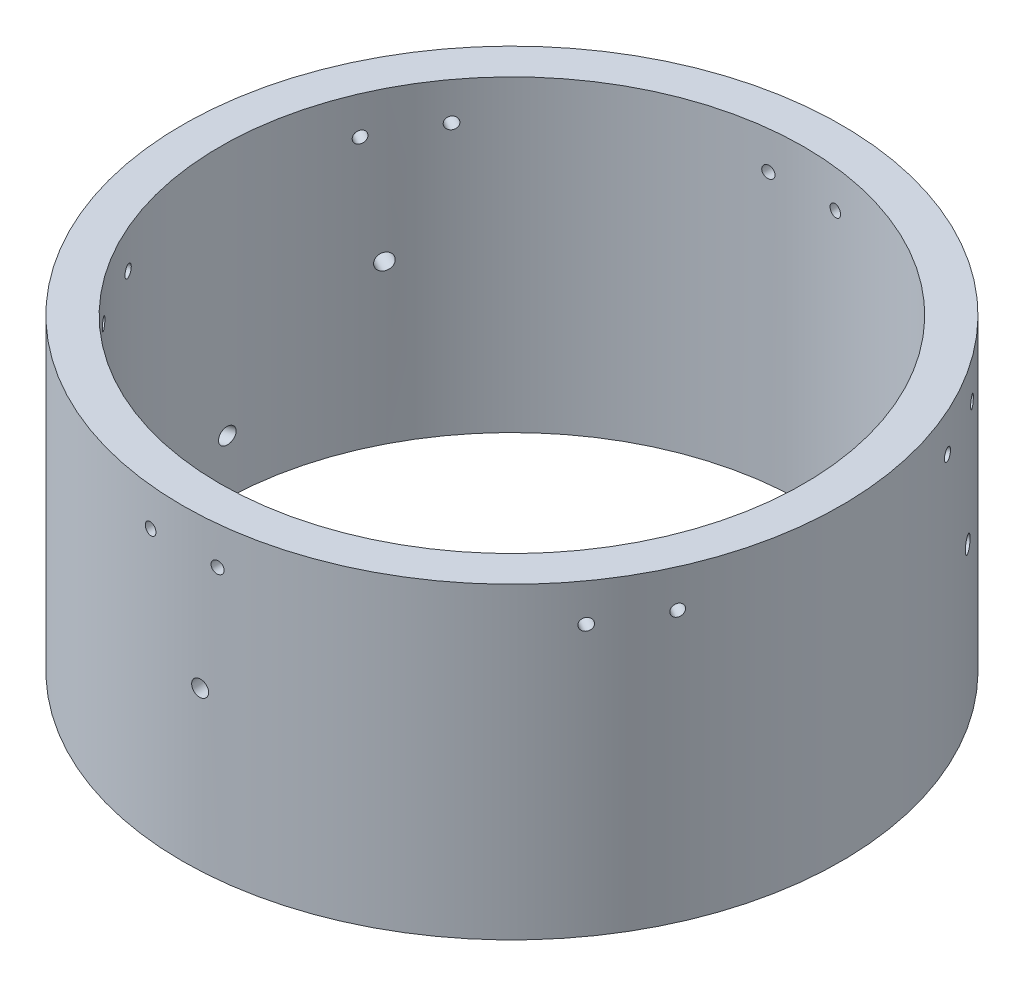
SolidWorks part; units mm, degrees
note: The reader was unsure of these and kept them because the rebuilt part matched: shared geometry of "Sketch1<6>".
material "6061 Alloy"
ref_plane "Front Plane" through (0, 0, 0) normal (0, 0, 1) x (1, 0, 0)
ref_plane "Top Plane" through (0, 0, 0) normal (0, 1, 0) x (1, 0, 0)
ref_plane "Right Plane" through (0, 0, 0) normal (1, 0, 0) x (0, 0, -1)
sketch "Sketch1" plane through (0, 0, 0) normal (0, 1, 0) x (1, 0, 0)
  line L0 (0, 0) -> (36.3914, -37.6844) construction
  line L1 (0, 0) -> (0, -26.075) construction
  line L2 (0, 0) -> (-29.7799, -10.254) construction
  circle A0 centre (0, 0) radius 49.2125
  circle A1 centre (0, 0) radius 55.5625
  circle A2 centre (36.3914, -37.6844) radius 1.0033
  dimension "D1" = 98.425
  dimension "D4" = 2.0066
  dimension "D3" = 52.3875
  dimension "D5" = 44
  dimension "D6" = 71
  dimension "D2" = 6.35
extrude "Boss-Extrude1" add sketch "Sketch1" along normal blind 51.9303 contours A2 | A1 A2 A0
sketch "Sketch2" plane through (0, 0, 0) normal (0, 0, 1) x (1, 0, 0)
  line L1 (55.5625, 51.9303) -> (-55.5625, 51.9303) construction
  line L2 (0, 0) -> (0, 58.801) construction
  line L5 (55.5625, 51.9303) -> (-55.5625, 51.9303)
  circle A0 centre (-5.6444, 45.5803) radius 1.0033
  dimension "D2" = 2.0066
  dimension "D3" = 5.6444
  dimension "D1" = 6.35
extrude "Cut-Extrude1" cut sketch "Sketch2" along normal up to surface (55.3683 mm away) contours A0
sketch "Sketch4" plane through (0, 0, 0) normal (0, 1, 0) x (1, 0, 0)
  line L0 (0, 0) -> (0, -25.6237) construction
  line L1 (0, 0) -> (1.2116, -23.1184)
  dimension "D1" = 3
ref_plane "Plane4" through (0, 0, 0) normal (0.0523, 0, 0.9986) x (0.9986, 0, -0.0523)
sketch "Sketch5" plane through (0, 0, 0) normal (0.0523, 0, 0.9986) x (0.9986, 0, -0.0523)
  circle A0 centre (0, 26.67) radius 1.3589
  dimension "D2" = 2.7178
  dimension "D1" = 26.67
extrude "Cut-Extrude5" cut sketch "Sketch5" along normal up to surface (55.5459 mm away) contours A0
mirror "Mirror1" about plane through (0, 0, 0) normal (1, 0, 0) of "Cut-Extrude1"
pattern_circular "CirPattern1" count 6 over 360 about axis through (0, 51.9303, 0) along (0, 1, 0) of "Cut-Extrude1", "Mirror1"
extrude "Cut-Extrude3" cut sketch "Sketch1<6>" along normal blind 5.08 contours A2
sketch "Sketch1<6>" plane through (0, 0, 0) normal (0, 1, 0) x (1, 0, 0) same geometry as "Sketch1"
ref_plane "Plane1" [suppressed] through (0, 25.9652, 0) normal (0, -1, 0) x (-1, 0, 0)
pattern_circular "CirPattern2" count 12 over 360 about axis through (0, 0, 0) along (0, 1, 0) of "Cut-Extrude3"
ref_plane "Plane2" through (-38.597, 0, -39.9683) normal (-0.6947, 0, -0.7193) x (-0.7193, 0, 0.6947)
pattern_circular "CirPattern3" count 3 over 360 about axis through (0, 51.9303, 0) along (0, 1, 0) of "Cut-Extrude5"
ref_plane "Plane3" through (0, 0, 0) normal (-0.9455, 0, 0.3256) x (0.3256, 0, 0.9455)
sketch "Sketch3" plane through (0, 0, 0) normal (-0.9455, 0, 0.3256) x (0.3256, 0, 0.9455)
  line L0 (0, 9.144) -> (-25.036, 9.144) construction
  line L1 (0, 9.144) -> (0, 0) construction
  circle A0 centre (0, 9.144) radius 3.6576
  circle A1 centre (-17.145, 9.144) radius 1.3589
  circle A2 centre (17.145, 9.144) radius 1.3589
  dimension "D2" = 7.3152
  dimension "D3" = 2.7178
  dimension "D1" = 9.144
  dimension "D4" = 17.145
extrude "Cut-Extrude4" cut sketch "Sketch3" along normal up to surface (55.442 mm away) contours A0 | A1 | A2
sketch "Sketch7" plane through (0, 0, 0) normal (0, -1, 0) x (1, 0, 0)
  circle A0 centre (-50.8314, 12.6737) radius 1.0033 construction
  circle A1 centre (0, 0) radius 55.5625
  circle A5 centre (0, 0) radius 55.5625
  circle A6 centre (-37.6844, 36.3914) radius 1.0033 construction
  circle A7 centre (-50.8314, 12.6737) radius 1.0033
  circle A8 centre (-37.6844, 36.3914) radius 1.0033
  arc A9 (-14.44, 50.3581) -> (12.6737, 50.8314) centre (0, 0) cw construction
  circle A10 centre (-0.9143, 52.3795) radius 1.5
  dimension "D1" = 0
  dimension "D2" = 3
extrude "Cut-Extrude6" cut sketch "Sketch7" against normal blind 6.35 contours A10
pattern_circular "CirPattern4" count 3 over 360 about axis through (0, 0, 0) along (0, 1, 0) of "Cut-Extrude6"
equation "\"Middle Coupler Inner Daimeter\"= 3.875in"
equation "\"Middle Coupler  Wall Thickness\" = 0.25in"
equation "\"Middle Coupler Bottom Thickness\"= 0.2in"
equation "\"Bearing Rail Offset\"= 0.45in"
equation "\"3-56 UNF Tap\"= 0.089in"
equation "\"3-56 UNF Clearance\"= 0.104in"
equation "\"Ball Bearing Distance\"= 0.03in"
equation "\"D2@Sketch1\"=\"Middle Coupler  Wall Thickness\""
equation "\"D2@Sketch2\"=\"3-48 Tap\""
equation "\"D3@Sketch2\"=1/4.5"
equation "\"D3@Sketch1\"=(\"Middle Coupler Inner Daimeter\"+\"D2@Sketch1\")/2"
equation "\"D4@Sketch1\"=\"3-48 Tap\""
equation "\"D1@Sketch1\"=\"Middle Coupler Inner Daimeter\""
equation "\"TCA Outer Diameter\" = 6in"
equation "\"Interstage Aeroframe Wall Thickness\" = 0.072in"
equation "\"Compression Spring OD\"= 0.42in"
equation "\"10-24 Tap\"= 0.157in"
equation "\"10-24 Clearance\"= 0.196in"
equation "\"Lower Stage Fuselage Wall Thickness\" = 0.25in"
equation "\"6-32 Tap\" = 0.107in"
equation "\"1/4-20 Tap\" = 0.201in"
equation "\"D1@Boss-Extrude1\"=1.595in - 0.0675+0.7-0.183"
equation "\"3-48 Tap\"= 0.079in"
equation "\"3-48 Clearance\" = 0.104in"
equation "\"6-32 Clearance\" = 0.144"
equation "\"12-24 Tap\" = 0.177in"
equation "\"D3@Sketch3\"=\"6-32 Tap\""
equation "\"D2@Sketch5\"=\"6-32 Tap\""
equation "\"D2@Sketch3\"=0.176 + 0.056*2"
